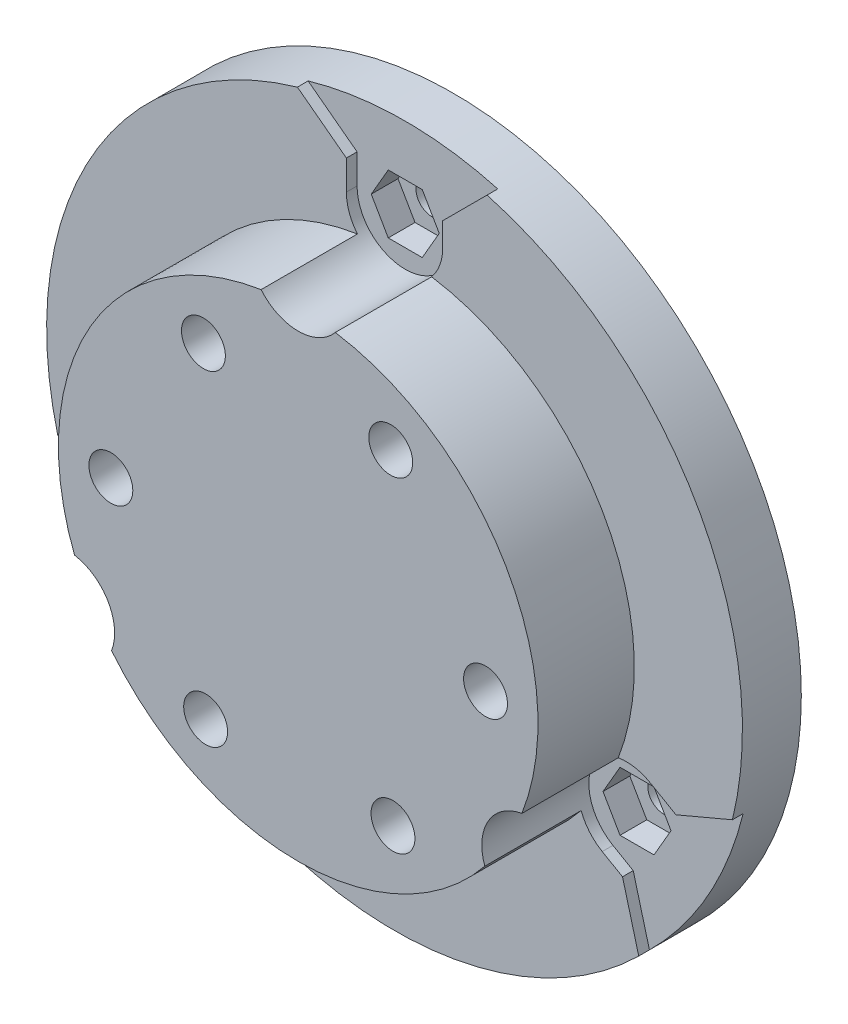
SolidWorks part; units mm, degrees
ref_plane "Front Plane" through (0, 0, 0) normal (0, 0, 1) x (1, 0, 0)
ref_plane "Top Plane" through (0, 0, 0) normal (0, 1, 0) x (1, 0, 0)
ref_plane "Right Plane" through (0, 0, 0) normal (1, 0, 0) x (0, 0, -1)
sketch "Sketch1" plane through (0, 0, 0) normal (0, 0, 1) x (1, 0, 0)
  circle A0 centre (0, 0) radius 10
  circle A1 centre (0, 0) radius 11
  circle A2 centre (0, 0) radius 8.6
  dimension "D1" = 20
  dimension "D2" = 22
  dimension "D3" = 2.4
sketch "Sketch2" plane through (0, 0, 0) normal (0, 0, 1) x (1, 0, 0)
  circle A0 centre (0, 0) radius 25 construction
  circle A1 centre (0, 0) radius 32.5
  dimension "D1" = 50
  dimension "D2" = 7.5
extrude "Boss-Extrude1" add sketch "Sketch2" along normal blind 10
sketch "Sketch3" plane through (0, 0, 0) normal (0, 0, 1) x (1, 0, 0)
  circle A0 centre (0, 25) radius 1.5
  circle A1 centre (0, 0) radius 25 construction
  dimension "D1" = 3
extrude "Cut-Extrude2" cut sketch "Sketch3" along normal through all both and the other way through all
sketch "Sketch4" plane through (0, 0, 10) normal (0, 0, 1) x (1, 0, 0)
  line L1 (1.5877, 22.25) -> (3.1754, 25)
  line L2 (3.1754, 25) -> (1.5877, 27.75)
  line L3 (1.5877, 27.75) -> (-1.5877, 27.75)
  line L4 (-1.5877, 27.75) -> (-3.1754, 25)
  line L5 (-3.1754, 25) -> (-1.5877, 22.25)
  line L6 (-1.5877, 22.25) -> (1.5877, 22.25)
  circle A1 centre (0, 25) radius 2.75 construction
  dimension "D1" = 5.5
extrude "Cut-Extrude3" cut sketch "Sketch4" against normal blind 8
sketch "Sketch5" plane through (0, 0, 10) normal (0, 0, 1) x (1, 0, 0)
  line L0 (4.5, 25) -> (4.5, 32.187)
  line L1 (-4.5, 25) -> (-4.5, 32.187)
  circle A1 centre (0, 0) radius 32.5 construction
  circle A2 centre (0, 25) radius 4.5
  arc A3 (-4.5, 25) -> (4.5, 25) centre (0, 25) ccw
  arc A4 (4.5, 32.187) -> (-4.5, 32.187) centre (0, 0) ccw
  dimension "D1" = 3
extrude "Cut-Extrude5" cut sketch "Sketch5" against normal offset from surface (5.5 mm away) 2.5 up to face at (1.5, 25, 2)
pattern_circular "CirPattern1" count 3 over 360 about axis through (0, 0, 10) along (0, 0, 1) of "Cut-Extrude2", "Cut-Extrude3", "Cut-Extrude5"
sketch "Sketch8" plane through (0, 0, 10) normal (0, 0, 1) x (1, 0, 0)
  circle A0 centre (0, 0) radius 22.4
  arc A1 (-30.1247, -12.1964) -> (-25.6247, -19.9906) centre (0, 0) ccw construction
  arc A2 (-25.6247, -19.9906) -> (25.6247, -19.9906) centre (0, 0) ccw construction
  arc A3 (25.6247, -19.9906) -> (30.1247, -12.1964) centre (0, 0) ccw construction
  arc A4 (30.1247, -12.1964) -> (4.5, 32.187) centre (0, 0) ccw construction
  arc A5 (-4.5, 32.187) -> (-30.1247, -12.1964) centre (0, 0) ccw construction
  arc A6 (4.5, 32.187) -> (-4.5, 32.187) centre (0, 0) ccw construction
  arc A7 (-30.1247, -12.1964) -> (-25.6247, -19.9906) centre (0, 0) ccw
  arc A8 (-25.6247, -19.9906) -> (25.6247, -19.9906) centre (0, 0) ccw
  arc A9 (25.6247, -19.9906) -> (30.1247, -12.1964) centre (0, 0) ccw
  arc A10 (30.1247, -12.1964) -> (4.5, 32.187) centre (0, 0) ccw
  arc A11 (-4.5, 32.187) -> (-30.1247, -12.1964) centre (0, 0) ccw
  arc A12 (4.5, 32.187) -> (-4.5, 32.187) centre (0, 0) ccw
  dimension "D1" = 44.8
extrude "Cut-Extrude8" cut sketch "Sketch8" against normal offset from surface (4.5 mm away) 1 up to face at (0, 27.5467, 4.5)
chamfer "Chamfer1" distance 5 angle 45 6 edges at (4.5, 32.187, 5) (-4.5, 32.187, 5) (30.1247, -12.1964, 5) (25.6247, -19.9906, 5) (-25.6247, -19.9906, 5) (-30.1247, -12.1964, 5) first distance on face at (4.5, 28.5935, 5) first distance on face at (32.5, 0, 0) first distance on face at (22.5127, -18.1939, 5) first distance on face at (-27.0127, -10.3996, 5)
sketch "Sketch7" plane through (0, 0, 0) normal (0, 0, -1) x (-1, 0, 0)
  circle A0 centre (0, 0) radius 6.1
  dimension "D1" = 12.2
extrude "Cut-Extrude7" cut sketch "Sketch7" against normal blind 4
sketch "Sketch9" plane through (0, 0, 10) normal (0, 0, 1) x (1, 0, 0)
  arc A6 (-3.4662, 22.1302) -> (3.4662, 22.1302) centre (0, 25) ccw
  arc A7 (-3.4662, 22.1302) -> (-20.8984, -8.0633) centre (0, 0) ccw
  arc A8 (-17.4322, -14.0669) -> (-20.8984, -8.0633) centre (-21.6506, -12.5) ccw
  arc A9 (-17.4322, -14.0669) -> (17.4322, -14.0669) centre (0, 0) ccw
  arc A10 (20.8984, -8.0633) -> (17.4322, -14.0669) centre (21.6506, -12.5) ccw
  arc A11 (20.8984, -8.0633) -> (3.4662, 22.1302) centre (0, 0) ccw
  arc A12 (-3.4662, 22.1302) -> (3.4662, 22.1302) centre (0, 25) ccw
  arc A13 (-3.4662, 22.1302) -> (-20.8984, -8.0633) centre (0, 0) ccw
  arc A14 (-17.4322, -14.0669) -> (-20.8984, -8.0633) centre (-21.6506, -12.5) ccw
  arc A15 (-17.4322, -14.0669) -> (17.4322, -14.0669) centre (0, 0) ccw
  arc A16 (20.8984, -8.0633) -> (17.4322, -14.0669) centre (21.6506, -12.5) ccw
  arc A17 (20.8984, -8.0633) -> (3.4662, 22.1302) centre (0, 0) ccw
  dimension "D1" = 0
extrude "Boss-Extrude2" add sketch "Sketch9" along normal blind 4.5
sketch "Sketch10" plane through (0, 0, 14.5) normal (0, 0, 1) x (1, 0, 0)
  circle A53 centre (0.1201, -17.4996) radius 2.05 construction
  circle A54 centre (-8.6457, -15.2152) radius 2.05
  circle A55 centre (-15.095, -8.8538) radius 2.05 construction
  circle A56 centre (-17.4996, -0.1201) radius 2.05
  circle A57 centre (-15.2152, 8.6457) radius 2.05 construction
  circle A58 centre (-8.8538, 15.095) radius 2.05
  arc A59 (-16.9366, -4.4046) -> (-12.1105, -12.6327) centre (0, 0) ccw
  arc A60 (-4.885, 16.8044) -> (-16.9366, -4.4046) centre (0, 0) ccw
  arc A61 (4.6538, 16.8699) -> (-4.885, 16.8044) centre (0, 0) ccw
  arc A62 (16.9955, -4.1716) -> (4.6538, 16.8699) centre (0, 0) ccw
  arc A63 (12.2828, -12.4652) -> (16.9955, -4.1716) centre (0, 0) ccw
  arc A64 (-12.1105, -12.6327) -> (12.2828, -12.4652) centre (0, 0) ccw
  arc A65 (-16.9366, -4.4046) -> (-12.1105, -12.6327) centre (0, 0) ccw construction
  arc A66 (-4.885, 16.8044) -> (-16.9366, -4.4046) centre (0, 0) ccw construction
  arc A67 (4.6538, 16.8699) -> (-4.885, 16.8044) centre (0, 0) ccw construction
  arc A68 (16.9955, -4.1716) -> (4.6538, 16.8699) centre (0, 0) ccw construction
  arc A69 (12.2828, -12.4652) -> (16.9955, -4.1716) centre (0, 0) ccw construction
  arc A70 (-12.1105, -12.6327) -> (12.2828, -12.4652) centre (0, 0) ccw construction
  circle A71 centre (-0.1201, 17.4996) radius 2.05 construction
  circle A72 centre (8.6457, 15.2152) radius 2.05
  circle A73 centre (15.095, 8.8538) radius 2.05 construction
  circle A74 centre (17.4996, 0.1201) radius 2.05
  circle A75 centre (15.2152, -8.6457) radius 2.05 construction
  circle A76 centre (8.8538, -15.095) radius 2.05
  point P27 (0, 0)
  dimension "D2" = 4.1
  dimension "D1" = 15
  dimension "D3" = 12
extrude "Cut-Extrude9" cut sketch "Sketch10" against normal blind 7.5
equation "\"Module\"= 1mm"
equation "\"Number of Teeth\"= 20"
equation "\"Planet diameter\"= ( \"Module\" * 30 )"
equation "\"M3\"= 3mm"
equation "\"D1@Sketch2\"=\"Module\"*\"Number of Teeth\"+\"Planet diameter\""
equation "\"D1@Sketch3\"=\"M3\""
equation "\"Carrier Width\"= 10mm"
equation "\"D1@Cut-Extrude3\"=\"Carrier Width\" - 2 "
